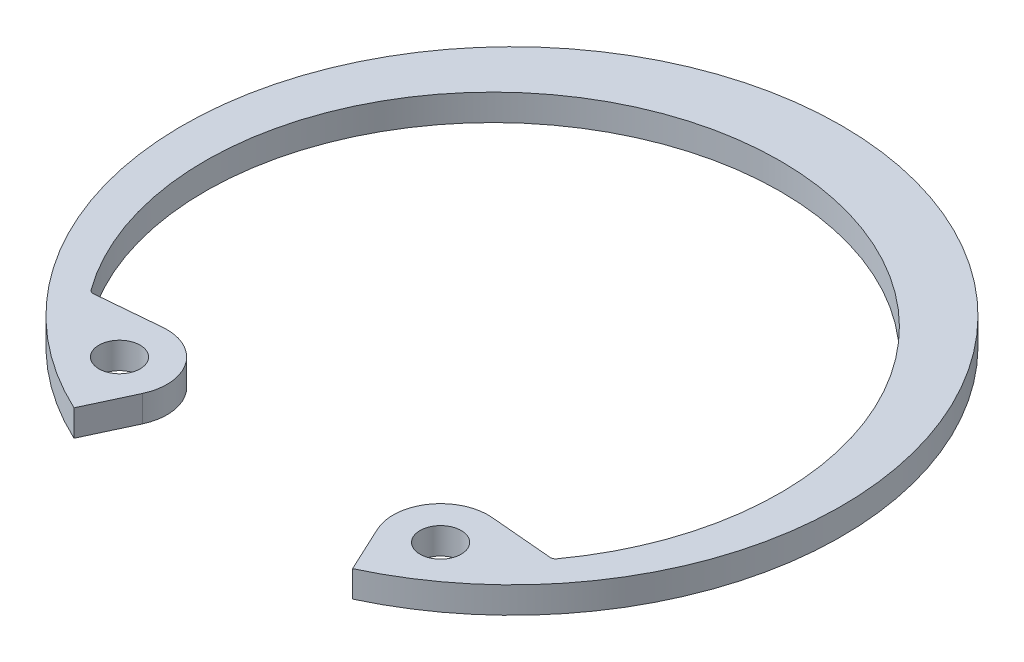
SolidWorks part; units mm, degrees
material "Cast Carbon Steel"
ref_plane "Front" through (0, 0, 0) normal (0, 0, 1) x (1, 0, 0)
ref_plane "Top" through (0, 0, 0) normal (0, 1, 0) x (1, 0, 0)
ref_plane "Right" through (0, 0, 0) normal (1, 0, 0) x (0, 0, -1)
sketch "Sketch2" plane through (0, 0, 0) normal (0, 1, 0) x (1, 0, 0)
  line L0 (0, 0) -> (0, -15.8623) construction
  line L1 (-11.1256, -9.1651) -> (-12.2431, -10.0856) construction
  line L2 (6.7037, -14.3761) -> (5.6557, -12.1286)
  line L3 (-6.7037, -14.3761) -> (-5.6557, -12.1286)
  line L4 (0, 12.9159) -> (0, 15.8623) construction
  line L5 (11.1256, -9.1651) -> (7.9267, -8.8852)
  line L6 (-11.1256, -9.1651) -> (-7.9267, -8.8852)
  line L7 (6.4263, -9.283) -> (-1.3986, -14.6999) construction
  line L8 (-1.3986, -14.6999) -> (1.2037, -18.4591) construction
  line L9 (1.2037, -18.4591) -> (9.0287, -13.0421) construction
  line L10 (6.4263, -9.283) -> (9.0287, -13.0421) construction
  line L11 (7.7275, -11.1625) -> (5.6557, -12.1286) construction
  line L12 (7.7275, -11.1625) -> (9.0287, -13.0421) construction
  line L13 (6.4263, -9.283) -> (-6.4263, -9.283) construction
  line L14 (-6.4263, -9.283) -> (-9.0287, -13.0421) construction
  arc A1 (6.7037, -14.3761) -> (-6.7037, -14.3761) centre (0, 0) ccw
  arc A2 (11.1256, -9.1651) -> (-11.1256, -9.1651) centre (0, -0.9274) ccw
  circle A3 centre (0, 0) radius 15.8623 construction
  arc A4 (5.6557, -12.1286) -> (7.9267, -8.8852) centre (7.7275, -11.1625) cw
  arc A5 (-5.6557, -12.1286) -> (-7.9267, -8.8852) centre (-7.7275, -11.1625) ccw
  circle A6 centre (7.7275, -11.1625) radius 0.9906
  circle A7 centre (-7.7275, -11.1625) radius 0.9906
  arc A8 (11.1256, -9.1651) -> (-11.1256, -9.1651) centre (0, -0.9274) cw construction
  circle A9 centre (0, 0) radius 9.906 construction
  point P5 (7.7275, -11.1625)
  point P10 (6.4263, -9.283)
  dimension "D1" = 60
  dimension "D2" = 60
  dimension "L" = 19.812
  dimension "R" = 1.9812
  dimension "Df" = 31.7246
  dimension "H" = 4.572
  dimension "Angle" = 25
  dimension "Sec. Max" = 2.9464
  dimension "Sec. Min" = 1.4478
extrude "Extrude1" add sketch "Sketch2" against normal blind 1.27
fillet "Fillet1" radius 0.254 2 edges at (-11.1256, -0.635, 9.1651) (11.1256, -0.635, 9.1651)
sketch "Sketch3" plane through (0, 0, 0) normal (1, 0, 0) x (0, 0, -1)
  line L0 (-14.2875, -22.1488) -> (-14.2875, -1.3462)
  line L1 (-14.2875, -1.3462) -> (-15.2019, -1.3462)
  line L2 (-15.2019, -1.3462) -> (-15.2019, 0.0762)
  line L3 (-15.2019, 0.0762) -> (-14.2875, 0.0762)
  line L4 (-14.2875, 0.0762) -> (-14.2875, 3.2512)
  line L5 (-14.2875, -22.1488) -> (-16.1163, -22.1488)
  line L6 (-14.2875, -1.3462) -> (0, -1.3462) construction
  line L7 (-14.2875, 3.2512) -> (-16.1163, 3.2512)
  line L8 (0, 130.3401) -> (0, 164.6301) construction
  line L9 (0, -1.3462) -> (0, 0.0762) construction
  line L10 (0, 0.0762) -> (-14.2875, 0.0762) construction
  line L11 (-15.2019, -0.635) -> (0, -0.635) construction
  line L12 (0, -135.0899) -> (0, 130.3401) construction
  line L13 (-9.0486, -1.27) -> (12.9159, -1.27) construction
  line L14 (-16.1163, -22.1488) -> (-16.1163, 3.2512)
  dimension "D1" = 0.635
  dimension "Shaft Lg" = 25.4
  dimension "Dg" = 30.4038
  dimension "Db" = 28.575
  dimension "W" = 1.4224
  dimension "D2" = 0.9144
  dimension "D3" = 3.175
  dimension "D4" = 0.9144
revolve "Revolve1" [suppressed] add sketch "Sketch3" angle 360 about L8
delete or keep bodies "Body-Delete1" [suppressed] type delete bodies bodies 116
ref_axis "Axis1" through (0, 0.0635, 0) along (0, -1, 0)
equation "\"D3@Sketch3\" = \"Shaft Lg@Sketch3\"/8"
equation "\"Shaft Lg@Sketch3\" = \"D1@Extrude1\"*20"
equation "\"D1@Sketch3\" = \"D1@Extrude1\"/2"
equation "\"D2@Sketch3\" = \"D4@Sketch3\""
